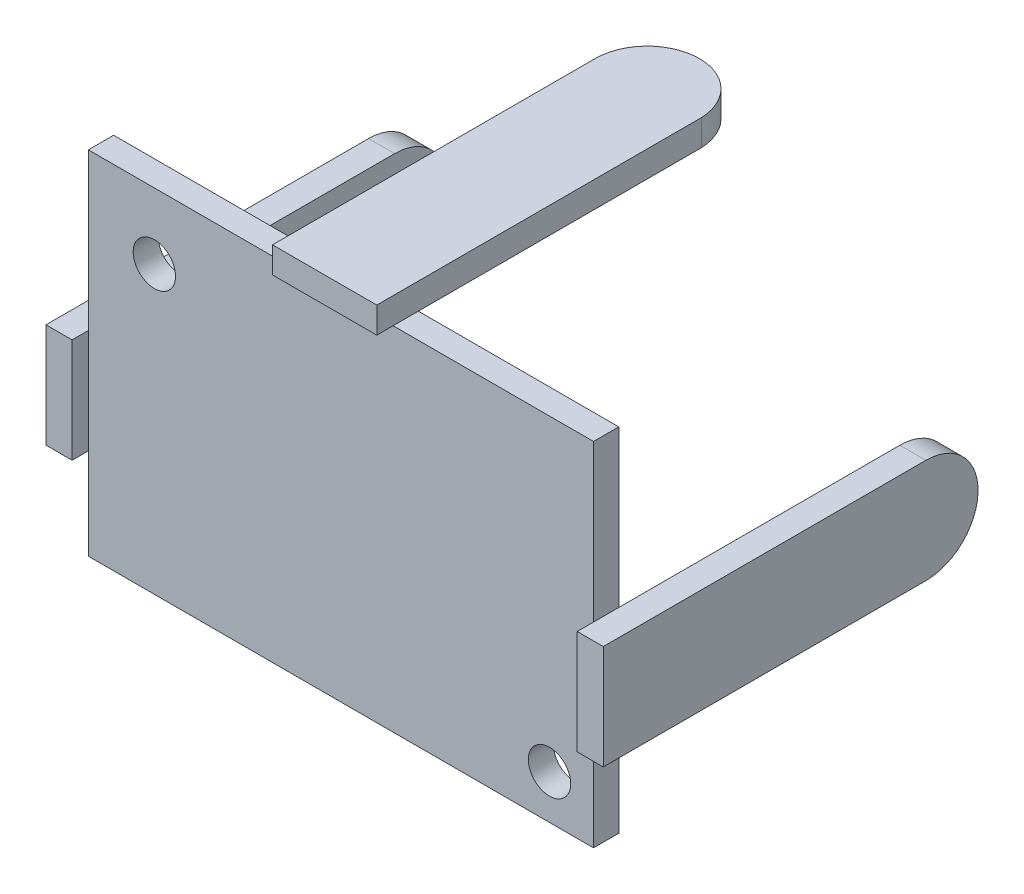
SolidWorks part; units mm, degrees
ref_plane "Front Plane" through (0, 0, 0) normal (0, 0, 1) x (1, 0, 0)
ref_plane "Top Plane" through (0, 0, 0) normal (0, 1, 0) x (1, 0, 0)
ref_plane "Right Plane" through (0, 0, 0) normal (1, 0, 0) x (0, 0, -1)
sketch "Sketch1" plane through (0, 0, 0) normal (0, 0, 1) x (1, 0, 0)
  line L0 (12.8, -8.1) -> (12.8, -10.8) construction
  line L1 (15.5, 10.8) -> (-15.5, 10.8)
  line L2 (15.5, 10.8) -> (15.5, -10.8)
  line L3 (15.5, -10.8) -> (-15.5, -10.8)
  line L4 (-15.5, 10.8) -> (-15.5, -10.8)
  line L5 (15.5, 10.8) -> (-15.5, -10.8) construction
  line L6 (15.5, -10.8) -> (-15.5, 10.8) construction
  line L7 (12.8, -8.1) -> (15.5, -8.1) construction
  circle A1 centre (12.8, -8.1) radius 1.3
  circle A2 centre (-11.45, 6.75) radius 1.3
  point P0 (0, 0)
  point P5 (-11.4876, 6.5681)
  dimension "D3" = 1.4
  dimension "D4" = 2.6
  dimension "D5" = 2.6
  dimension "D6" = 2.75
  dimension "D7" = 1.4
  dimension "D8" = 1.4
  dimension "D1" = 21.6
  dimension "D2" = 31
  dimension "D9" = 2.75
extrude "Boss-Extrude1" add sketch "Sketch1" along normal blind 1.55
sketch "Sketch2" plane through (0, 0, 0) normal (1, 0, 0) x (0, 0, -1)
  line L0 (-1.8605, 0.7) -> (28.5002, 0.7) construction
  line L1 (-2.55, 1.2) -> (17.249, 1.2)
  line L2 (-2.55, 1.2) -> (-2.55, -5.2)
  line L3 (-2.55, -5.2) -> (17.3641, -5.2)
  line L4 (20.45, 1.2) -> (20.45, -5.2) construction
  line L5 (-1.55, -10.8) -> (0, -10.8) construction
  line L6 (-1.55, -10.8) -> (-1.55, 10.8) construction
  arc A0 (17.249, 1.2) -> (17.3641, -5.2) centre (17.249, -2.001) cw
  point P13 (17.3641, -5.2)
  dimension "D6" = 3.201
  dimension "D1" = 23
  dimension "D2" = 11.5
  dimension "D3" = 0.5
  dimension "D4" = 6.4
  dimension "D5" = 1
extrude "Boss-Extrude2" add sketch "Sketch2" along normal blind 1.6 from surface starting at face at (15.5, 0, 0.775)
extrude "Boss-Extrude3" add sketch "Sketch2<2>" against normal blind 1.6 from surface starting at face at (-15.5, 0, 0.775)
sketch "Sketch2<2>" plane through (0, 0, 0) normal (1, 0, 0) x (0, 0, -1) same geometry as "Sketch2"
sketch "Sketch3" plane through (0, 10.8, 0) normal (0, 1, 0) x (1, 0, 0)
  line L0 (-2.7, -21.1313) -> (-2.7, 20.45) construction
  line L1 (-3.2, -2.55) -> (-3.2, 17.249)
  line L2 (-3.2, -2.55) -> (3.2, -2.55)
  line L3 (3.2, -2.55) -> (3.2, 17.3641)
  line L4 (-5.646, 20.45) -> (7.066, 20.45) construction
  line L5 (15.5, -1.55) -> (-15.5, -1.55) construction
  arc A0 (-3.2, 17.249) -> (3.2, 17.3641) centre (0.001, 17.249) cw
  point P6 (3.3523, -2.8686)
  point P7 (7.2264, 19.448)
  point P8 (10.1723, 19.2059)
  point P9 (-6.898, 19.3259)
  point P13 (5.8139, 18.8023)
  point P14 (-3.9521, 18.8023)
  point P15 (0, -2.55)
  dimension "D6" = 3.201
  dimension "D1" = 23
  dimension "D2" = 1
  dimension "D3" = 0.5
  dimension "D4" = 6.4
extrude "Boss-Extrude4" add sketch "Sketch3" along normal blind 1.6
